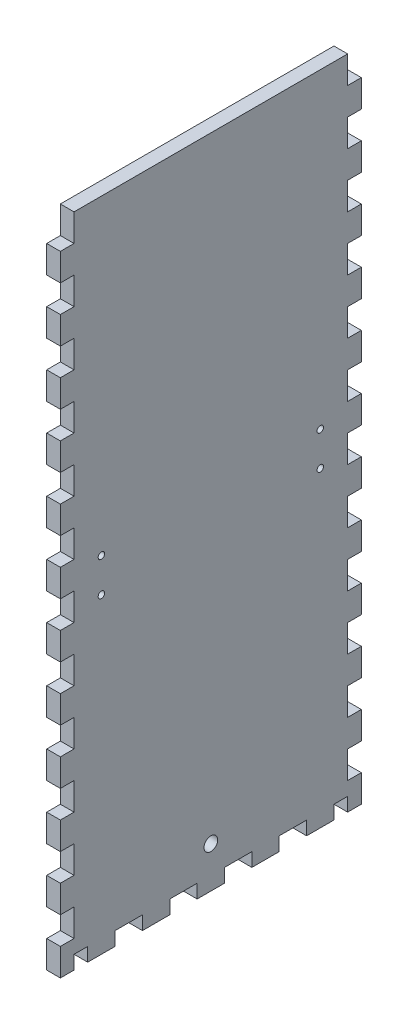
SolidWorks part; units mm, degrees
material "Acrylic (Medium-high impact)"
ref_plane "Front Plane" through (0, 0, 0) normal (0, 0, 1) x (1, 0, 0)
ref_plane "Top Plane" through (0, 0, 0) normal (0, 1, 0) x (1, 0, 0)
ref_plane "Right Plane" through (0, 0, 0) normal (1, 0, 0) x (0, 0, -1)
sketch "Sketch1" plane through (0, 0, 0) normal (0, 1, 0) x (1, 0, 0)
  line L1 (-136.525, 69.85) -> (136.525, 69.85)
  line L2 (-136.525, 69.85) -> (-136.525, -69.85)
  line L3 (-136.525, -69.85) -> (136.525, -69.85)
  line L4 (136.525, 69.85) -> (136.525, -69.85)
  point P4 (-136.525, 0)
  point P6 (0, 69.85)
  dimension "D1" = 139.7
  dimension "D2" = 273.05
extrude "Boss-Extrude1" add sketch "Sketch1" along normal blind 6.35
sketch "Sketch2" plane through (0, 6.35, 0) normal (0, 1, 0) x (1, 0, 0)
  line L0 (136.525, -69.85) -> (136.525, 69.85) construction
  line L1 (-136.525, 69.85) -> (136.525, 69.85)
  line L2 (-136.525, 69.85) -> (-136.525, -69.85)
  line L3 (-136.525, -69.85) -> (136.525, -69.85)
  line L4 (136.525, 69.85) -> (136.525, -69.85)
  line L5 (-136.525, -69.85) -> (136.525, -69.85) construction
  line L7 (-130.175, 63.5) -> (130.175, 63.5)
  line L8 (-130.175, 63.5) -> (-130.175, -63.5)
  line L9 (-130.175, -63.5) -> (130.175, -63.5)
  line L10 (130.175, 63.5) -> (130.175, -63.5)
  point P7 (-130.175, 0)
  point P14 (-136.525, 0)
  point P15 (0, -63.5)
  point P16 (0, -69.85)
  point P17 (130.175, 0)
  point P18 (136.525, 0)
  dimension "D1" = 6.35
  dimension "D2" = 6.35
extrude "Boss-Extrude2" add sketch "Sketch2" along normal blind 298.45
sketch "Sketch3" plane through (0, 0, 69.85) normal (0, 0, 1) x (1, 0, 0)
  line L0 (-25.273, 304.8) -> (-25.273, 0) construction
  line L2 (-130.175, 6.35) -> (130.175, 6.35) construction
  line L4 (-28.575, 283.21) -> (-28.575, 6.35)
  line L5 (-28.575, 6.35) -> (-21.971, 6.35)
  line L6 (-21.971, 292.354) -> (-21.971, 6.35)
  line L7 (-21.971, 292.354) -> (-41.529, 292.354)
  line L9 (-31.115, 285.75) -> (-41.529, 285.75)
  line L10 (-41.529, 292.354) -> (-41.529, 285.75)
  line L11 (-21.971, 101.6) -> (-9.271, 101.6) construction
  line L12 (-136.525, 0) -> (136.525, 0) construction
  line L13 (-12.446, 88.9) -> (-12.446, 101.6) construction
  line L14 (-15.621, 88.9) -> (-9.271, 88.9)
  line L15 (-15.621, 88.9) -> (-15.621, 71.9667)
  line L16 (-15.621, 71.9667) -> (-9.271, 71.9667)
  line L17 (-9.271, 88.9) -> (-9.271, 71.9667)
  line L18 (-15.621, 42.3333) -> (-9.271, 42.3333)
  line L19 (-15.621, 42.3333) -> (-15.621, 59.2667)
  line L20 (-15.621, 59.2667) -> (-9.271, 59.2667)
  line L21 (-9.271, 42.3333) -> (-9.271, 59.2667)
  line L26 (-15.621, 29.6333) -> (-9.271, 29.6333)
  line L27 (-15.621, 29.6333) -> (-15.621, 12.7)
  line L28 (-15.621, 12.7) -> (-9.271, 12.7)
  line L29 (-9.271, 29.6333) -> (-9.271, 12.7)
  line L30 (-12.446, 59.2667) -> (-12.446, 71.9667) construction
  line L31 (-12.446, 29.6333) -> (-12.446, 42.3333) construction
  line L32 (-12.446, 12.7) -> (-12.446, 0) construction
  line L33 (-136.525, 304.8) -> (136.525, 304.8) construction
  line L34 (-130.175, 304.8) -> (-130.175, 6.35) construction
  arc A0 (-28.575, 283.21) -> (-31.115, 285.75) centre (-31.115, 283.21) ccw
  point P5 (-25.273, 6.35)
  dimension "D5" = 2.54
  dimension "D1" = 6.604
  dimension "D2" = 12.954
  dimension "D3" = 6.604
  dimension "D4" = 286.004
  dimension "D6" = 101.6
  dimension "D7" = 12.7
  dimension "D8" = 12.7
  dimension "D9" = 6.35
  dimension "D10" = 101.6
extrude "Door Slot" cut sketch "Sketch3" against normal blind 12.7
sketch "Sketch4" plane through (0, 0, -63.5) normal (0, 0, 1) x (1, 0, 0)
  line L0 (-136.525, 304.8) -> (136.525, 304.8) construction
  line L1 (-47.879, 304.8) -> (-41.529, 304.8)
  line L2 (-47.879, 304.8) -> (-47.879, 6.35)
  line L3 (-47.879, 6.35) -> (-41.529, 6.35)
  line L4 (-41.529, 304.8) -> (-41.529, 6.35)
  line L5 (-18.796, 263.525) -> (-18.796, 247.65) construction
  line L6 (-41.529, 292.354) -> (-41.529, 285.75) construction
  line L7 (-21.971, 304.8) -> (-15.621, 304.8)
  line L8 (-21.971, 304.8) -> (-21.971, 6.35)
  line L9 (-21.971, 6.35) -> (-15.621, 6.35)
  line L10 (-15.621, 304.8) -> (-15.621, 6.35)
  line L11 (130.175, 6.35) -> (-130.175, 6.35) construction
  line L12 (-21.971, 6.35) -> (-21.971, 292.354) construction
  line L13 (-41.529, 304.8) -> (-47.879, 304.8)
  line L14 (-41.529, 304.8) -> (-41.529, 292.1)
  line L15 (-41.529, 292.1) -> (-47.879, 292.1)
  line L16 (-47.879, 304.8) -> (-47.879, 292.1)
  line L17 (-41.529, 276.225) -> (-47.879, 276.225)
  line L18 (-41.529, 276.225) -> (-41.529, 263.525)
  line L19 (-41.529, 263.525) -> (-47.879, 263.525)
  line L20 (-47.879, 276.225) -> (-47.879, 263.525)
  line L21 (-47.879, 6.35) -> (-41.529, 6.35)
  line L22 (-47.879, 6.35) -> (-47.879, 19.05)
  line L23 (-47.879, 19.05) -> (-41.529, 19.05)
  line L24 (-41.529, 6.35) -> (-41.529, 19.05)
  line L25 (-47.879, 34.925) -> (-41.529, 34.925)
  line L26 (-47.879, 34.925) -> (-47.879, 47.625)
  line L27 (-47.879, 47.625) -> (-41.529, 47.625)
  line L28 (-41.529, 34.925) -> (-41.529, 47.625)
  line L29 (-47.879, 92.075) -> (-41.529, 92.075)
  line L30 (-47.879, 92.075) -> (-47.879, 104.775)
  line L31 (-47.879, 104.775) -> (-41.529, 104.775)
  line L32 (-41.529, 92.075) -> (-41.529, 104.775)
  line L33 (-47.879, 149.225) -> (-41.529, 149.225)
  line L34 (-47.879, 149.225) -> (-47.879, 161.925)
  line L35 (-47.879, 161.925) -> (-41.529, 161.925)
  line L36 (-41.529, 149.225) -> (-41.529, 161.925)
  line L37 (-47.879, 177.8) -> (-41.529, 177.8)
  line L38 (-47.879, 177.8) -> (-47.879, 190.5)
  line L39 (-47.879, 190.5) -> (-41.529, 190.5)
  line L40 (-41.529, 177.8) -> (-41.529, 190.5)
  line L41 (-47.879, 206.375) -> (-41.529, 206.375)
  line L42 (-47.879, 206.375) -> (-47.879, 219.075)
  line L43 (-47.879, 219.075) -> (-41.529, 219.075)
  line L44 (-41.529, 206.375) -> (-41.529, 219.075)
  line L45 (-47.879, 234.95) -> (-41.529, 234.95)
  line L46 (-47.879, 234.95) -> (-47.879, 247.65)
  line L47 (-47.879, 247.65) -> (-41.529, 247.65)
  line L48 (-41.529, 234.95) -> (-41.529, 247.65)
  line L49 (-41.529, 133.35) -> (-47.879, 133.35)
  line L50 (-41.529, 133.35) -> (-41.529, 120.65)
  line L51 (-41.529, 120.65) -> (-47.879, 120.65)
  line L52 (-47.879, 133.35) -> (-47.879, 120.65)
  line L53 (-41.529, 76.2) -> (-47.879, 76.2)
  line L54 (-41.529, 76.2) -> (-41.529, 63.5)
  line L55 (-41.529, 63.5) -> (-47.879, 63.5)
  line L56 (-47.879, 76.2) -> (-47.879, 63.5)
  line L57 (-44.704, 304.8) -> (-44.704, 292.1) construction
  line L58 (-44.704, 292.1) -> (-44.704, 276.225) construction
  line L59 (-44.704, 276.225) -> (-44.704, 263.525) construction
  line L60 (-44.704, 247.65) -> (-44.704, 234.95) construction
  line L61 (-44.704, 234.95) -> (-44.704, 219.075) construction
  line L62 (-44.704, 219.075) -> (-44.704, 206.375) construction
  line L63 (-44.704, 206.375) -> (-44.704, 190.5) construction
  line L64 (-44.704, 190.5) -> (-44.704, 177.8) construction
  line L65 (-44.704, 177.8) -> (-44.704, 161.925) construction
  line L66 (-44.704, 161.925) -> (-44.704, 149.225) construction
  line L67 (-44.704, 133.35) -> (-44.704, 120.65) construction
  line L68 (-44.704, 120.65) -> (-44.704, 104.775) construction
  line L69 (-44.704, 104.775) -> (-44.704, 92.075) construction
  line L70 (-44.704, 92.075) -> (-44.704, 76.2) construction
  line L71 (-44.704, 76.2) -> (-44.704, 63.5) construction
  line L72 (-44.704, 63.5) -> (-44.704, 47.625) construction
  line L73 (-44.704, 47.625) -> (-44.704, 34.925) construction
  line L74 (-44.704, 34.925) -> (-44.704, 19.05) construction
  line L75 (-44.704, 19.05) -> (-44.704, 6.35) construction
  line L76 (-44.704, 149.225) -> (-44.704, 133.35) construction
  line L77 (-44.704, 263.525) -> (-44.704, 247.65) construction
  line L78 (-31.75, 304.8) -> (-31.75, 0) construction
  line L79 (136.525, 304.8) -> (-136.525, 304.8) construction
  line L80 (136.525, 0) -> (-136.525, 0) construction
  line L81 (-31.75, 8.3493) -> (-21.971, 8.3493) construction
  line L82 (-31.75, 8.3493) -> (-41.529, 8.3493) construction
  line L83 (-18.796, 149.225) -> (-18.796, 133.35) construction
  line L84 (-18.796, 19.05) -> (-18.796, 6.35) construction
  line L85 (-18.796, 34.925) -> (-18.796, 19.05) construction
  line L86 (-18.796, 47.625) -> (-18.796, 34.925) construction
  line L87 (-18.796, 63.5) -> (-18.796, 47.625) construction
  line L88 (-18.796, 76.2) -> (-18.796, 63.5) construction
  line L89 (-18.796, 92.075) -> (-18.796, 76.2) construction
  line L90 (-18.796, 104.775) -> (-18.796, 92.075) construction
  line L91 (-18.796, 120.65) -> (-18.796, 104.775) construction
  line L92 (-18.796, 133.35) -> (-18.796, 120.65) construction
  line L93 (-18.796, 161.925) -> (-18.796, 149.225) construction
  line L94 (-18.796, 177.8) -> (-18.796, 161.925) construction
  line L95 (-18.796, 190.5) -> (-18.796, 177.8) construction
  line L96 (-18.796, 206.375) -> (-18.796, 190.5) construction
  line L97 (-18.796, 219.075) -> (-18.796, 206.375) construction
  line L98 (-18.796, 234.95) -> (-18.796, 219.075) construction
  line L99 (-18.796, 247.65) -> (-18.796, 234.95) construction
  line L100 (-18.796, 276.225) -> (-18.796, 263.525) construction
  line L101 (-18.796, 292.1) -> (-18.796, 276.225) construction
  line L102 (-18.796, 304.8) -> (-18.796, 292.1) construction
  line L103 (-15.621, 76.2) -> (-15.621, 63.5)
  line L104 (-21.971, 63.5) -> (-15.621, 63.5)
  line L105 (-21.971, 76.2) -> (-21.971, 63.5)
  line L106 (-21.971, 76.2) -> (-15.621, 76.2)
  line L107 (-15.621, 133.35) -> (-15.621, 120.65)
  line L108 (-21.971, 120.65) -> (-15.621, 120.65)
  line L109 (-21.971, 133.35) -> (-21.971, 120.65)
  line L110 (-21.971, 133.35) -> (-15.621, 133.35)
  line L111 (-21.971, 234.95) -> (-21.971, 247.65)
  line L112 (-15.621, 247.65) -> (-21.971, 247.65)
  line L113 (-15.621, 234.95) -> (-15.621, 247.65)
  line L114 (-15.621, 234.95) -> (-21.971, 234.95)
  line L115 (-21.971, 206.375) -> (-21.971, 219.075)
  line L116 (-15.621, 219.075) -> (-21.971, 219.075)
  line L117 (-15.621, 206.375) -> (-15.621, 219.075)
  line L118 (-15.621, 206.375) -> (-21.971, 206.375)
  line L119 (-21.971, 177.8) -> (-21.971, 190.5)
  line L120 (-15.621, 190.5) -> (-21.971, 190.5)
  line L121 (-15.621, 177.8) -> (-15.621, 190.5)
  line L122 (-15.621, 177.8) -> (-21.971, 177.8)
  line L123 (-21.971, 149.225) -> (-21.971, 161.925)
  line L124 (-15.621, 161.925) -> (-21.971, 161.925)
  line L125 (-15.621, 149.225) -> (-15.621, 161.925)
  line L126 (-15.621, 149.225) -> (-21.971, 149.225)
  line L127 (-21.971, 92.075) -> (-21.971, 104.775)
  line L128 (-15.621, 104.775) -> (-21.971, 104.775)
  line L129 (-15.621, 92.075) -> (-15.621, 104.775)
  line L130 (-15.621, 92.075) -> (-21.971, 92.075)
  line L131 (-21.971, 34.925) -> (-21.971, 47.625)
  line L132 (-15.621, 47.625) -> (-21.971, 47.625)
  line L133 (-15.621, 34.925) -> (-15.621, 47.625)
  line L134 (-15.621, 34.925) -> (-21.971, 34.925)
  line L135 (-21.971, 6.35) -> (-21.971, 19.05)
  line L136 (-15.621, 19.05) -> (-21.971, 19.05)
  line L137 (-15.621, 6.35) -> (-15.621, 19.05)
  line L138 (-15.621, 6.35) -> (-21.971, 6.35)
  line L139 (-15.621, 276.225) -> (-15.621, 263.525)
  line L140 (-21.971, 263.525) -> (-15.621, 263.525)
  line L141 (-21.971, 276.225) -> (-21.971, 263.525)
  line L142 (-21.971, 276.225) -> (-15.621, 276.225)
  line L143 (-15.621, 304.8) -> (-15.621, 292.1)
  line L144 (-21.971, 292.1) -> (-15.621, 292.1)
  line L145 (-21.971, 304.8) -> (-21.971, 292.1)
  line L146 (-21.971, 304.8) -> (-15.621, 304.8)
  line L147 (-21.971, 304.8) -> (-21.971, 6.35)
  line L148 (-15.621, 6.35) -> (-21.971, 6.35)
  line L149 (-15.621, 304.8) -> (-15.621, 6.35)
  line L150 (-15.621, 304.8) -> (-21.971, 304.8)
  point P14 (-41.529, 289.052)
  dimension "D1" = 6.35
  dimension "D2" = 12.7
extrude "Door Guide Holes" cut sketch "Sketch4" against normal up to next contours L17 L4 L15 L2 | L2 L47 L4 L19 | L45 L2 L43 L4 | L41 L2 L39 L4 | L37 L2 L35 L4 | L49 L4 L33 L2 | L4 L51 L2 L31 | L53 L4 L29 L2 | L4 L55 L2 L27 | L25 L2 L23 L4 region at (-44.704, 284.1625, -63.5) region at (-44.704, 255.5875, -63.5) region at (-44.704, 227.0125, -63.5) region at (-44.704, 198.4375, -63.5) region at (-44.704, 169.8625, -63.5) region at (-44.704, 141.2875, -63.5) region at (-44.704, 112.7125, -63.5) region at (-44.704, 84.1375, -63.5) region at (-44.704, 55.5625, -63.5) region at (-44.704, 26.9875, -63.5)
ref_plane "Plane1" through (-31.75, 0, 0) normal (-1, 0, 0) x (0, 0, 1)
mirror "Mirror1" about plane through (-31.75, 0, 0) normal (-1, 0, 0) of "Door Guide Holes"
sketch "Lever Holes" plane through (0, 0, 69.85) normal (0, 0, 1) x (1, 0, 0)
  line L0 (49.276, 31.75) -> (58.928, 31.75)
  line L1 (49.276, 31.75) -> (49.276, 25.4)
  line L2 (49.276, 25.4) -> (58.928, 25.4)
  line L3 (58.928, 31.75) -> (58.928, 25.4)
  line L4 (36.1315, 19.05) -> (42.4815, 19.05)
  line L5 (36.1315, 19.05) -> (36.1315, 12.7)
  line L6 (36.1315, 12.7) -> (42.4815, 12.7)
  line L7 (42.4815, 19.05) -> (42.4815, 12.7)
  line L8 (65.7225, 19.05) -> (72.0725, 19.05)
  line L9 (65.7225, 19.05) -> (65.7225, 12.7)
  line L10 (65.7225, 12.7) -> (72.0725, 12.7)
  line L11 (72.0725, 19.05) -> (72.0725, 12.7)
  line L12 (42.4815, 15.875) -> (65.7225, 15.875) construction
  line L13 (-136.525, 0) -> (136.525, 0) construction
  line L14 (-21.971, 6.35) -> (130.175, 6.35) construction
  line L15 (130.175, 6.35) -> (-130.175, 6.35) construction
  point P12 (54.102, 15.875)
  point P13 (54.102, 25.4)
  point P24 (54.102, 6.35)
  dimension "D1" = 9.652
  dimension "D2" = 6.35
  dimension "D3" = 6.35
  dimension "D4" = 6.35
  dimension "D5" = 23.241
  dimension "D6" = 25.4
  dimension "D7" = 12.7
extrude "Cut-Extrude1" cut sketch "Lever Holes" against normal through all
sketch "Sketch7" plane through (136.525, 0, 0) normal (1, 0, 0) x (0, 0, -1)
  line L0 (-37.211, 92.583) -> (37.211, 92.583)
  line L1 (-37.211, 92.583) -> (-37.211, 18.161)
  line L2 (-37.211, 18.161) -> (37.211, 18.161)
  line L3 (37.211, 92.583) -> (37.211, 18.161)
  line L4 (-69.85, 0) -> (69.85, 0) construction
  circle A0 centre (0, 55.372) radius 26.9875
  circle A1 centre (-37.211, 92.583) radius 3.175
  circle A2 centre (37.211, 92.583) radius 3.175
  circle A3 centre (-37.211, 18.161) radius 3.175
  circle A4 centre (37.211, 18.161) radius 3.175
  point P9 (0, 18.161)
  point P10 (-37.211, 55.372)
  dimension "D3" = 53.975
  dimension "D4" = 6.35
  dimension "D1" = 74.422
  dimension "D2" = 55.372
extrude "Cut-Extrude2" cut sketch "Sketch7" against normal up to next contours A0 | L0 A1 L1 | L1 A1 L0 | L3 A2 L0 | L0 A2 L3 | L2 A3 L1 | L1 A3 L2 | L2 A4 L3 | L3 A4 L2 region at (136.525, 93.0322, 37.6602) region at (136.525, 91.2355, 35.8635) region at (136.525, 93.0322, -37.6602) region at (136.525, 91.2355, -35.8635) region at (136.525, 19.5085, 35.8635) region at (136.525, 17.7118, 37.6602) region at (136.525, 17.7118, -37.6602) region at (136.525, 19.5085, -35.8635) region at (136.525, 55.372, 0)
sketch "Sketch8" plane through (-136.525, 0, 0) normal (-1, 0, 0) x (0, 0, 1)
  line L0 (-69.85, 0) -> (69.85, 0) construction
  line L1 (-50.8, 160.275) -> (-50.8, 144.525) construction
  line L2 (-69.85, 304.8) -> (-69.85, 0) construction
  line L3 (0, -150.1775) -> (0, 150.1775) construction
  circle A0 centre (0, 19.05) radius 3.175
  circle A1 centre (-50.8, 160.275) radius 1.5
  circle A2 centre (-50.8, 144.525) radius 1.5
  circle A3 centre (50.8, 144.525) radius 1.5
  circle A4 centre (50.8, 160.275) radius 1.5
  point P6 (0, 0)
  point P12 (-50.8, 152.4)
  point P13 (-69.85, 152.4)
  dimension "D1" = 6.35
  dimension "D4" = 3
  dimension "D2" = 19.05
  dimension "D3" = 15.75
  dimension "D5" = 19.05
extrude "Cut-Extrude3" cut sketch "Sketch8" against normal up to next
sketch "Bottom" plane through (0, 0, 0) normal (0, -1, 0) x (1, 0, 0)
  line L0 (-130.175, 63.5) -> (130.175, 63.5) construction
  line L1 (-136.525, 69.85) -> (-122.1539, 69.85)
  line L2 (-136.525, 69.85) -> (-136.525, 63.5)
  line L3 (-136.525, 63.5) -> (-122.1539, 63.5)
  line L4 (-122.1539, 69.85) -> (-122.1539, 63.5)
  line L5 (-122.1539, 69.85) -> (-107.7829, 69.85)
  line L6 (-122.1539, 69.85) -> (-122.1539, 63.5)
  line L7 (-122.1539, 63.5) -> (-107.7829, 63.5)
  line L8 (-107.7829, 69.85) -> (-107.7829, 63.5)
  line L9 (-107.7829, 69.85) -> (-93.4118, 69.85)
  line L10 (-107.7829, 69.85) -> (-107.7829, 63.5)
  line L11 (-107.7829, 63.5) -> (-93.4118, 63.5)
  line L12 (-93.4118, 69.85) -> (-93.4118, 63.5)
  line L13 (-93.4118, 69.85) -> (-79.0408, 69.85)
  line L14 (-93.4118, 69.85) -> (-93.4118, 63.5)
  line L15 (-93.4118, 63.5) -> (-79.0408, 63.5)
  line L16 (-79.0408, 69.85) -> (-79.0408, 63.5)
  line L17 (-136.525, 69.85) -> (136.525, 69.85) construction
  line L18 (-41.529, 63.5) -> (-21.971, 63.5) construction
  line L19 (-79.0408, 69.85) -> (-64.6697, 69.85)
  line L20 (-79.0408, 69.85) -> (-79.0408, 63.5)
  line L21 (-79.0408, 63.5) -> (-64.6697, 63.5)
  line L22 (-64.6697, 69.85) -> (-64.6697, 63.5)
  line L23 (-64.6697, 69.85) -> (-50.2987, 69.85)
  line L24 (-64.6697, 69.85) -> (-64.6697, 63.5)
  line L25 (-64.6697, 63.5) -> (-50.2987, 63.5)
  line L26 (-50.2987, 69.85) -> (-50.2987, 63.5)
  line L27 (-50.2987, 69.85) -> (-35.9276, 69.85)
  line L28 (-50.2987, 69.85) -> (-50.2987, 63.5)
  line L29 (-50.2987, 63.5) -> (-35.9276, 63.5)
  line L30 (-35.9276, 69.85) -> (-35.9276, 63.5)
  line L31 (-35.9276, 69.85) -> (-21.5566, 69.85)
  line L32 (-35.9276, 69.85) -> (-35.9276, 63.5)
  line L33 (-35.9276, 63.5) -> (-21.5566, 63.5)
  line L34 (-21.5566, 69.85) -> (-21.5566, 63.5)
  line L36 (-21.5566, 69.85) -> (-7.1855, 69.85)
  line L37 (-21.5566, 69.85) -> (-21.5566, 63.5)
  line L38 (-21.5566, 63.5) -> (-7.1855, 63.5)
  line L39 (-7.1855, 69.85) -> (-7.1855, 63.5)
  line L40 (-7.1855, 69.85) -> (7.1855, 69.85)
  line L41 (-7.1855, 69.85) -> (-7.1855, 63.5)
  line L42 (-7.1855, 63.5) -> (7.1855, 63.5)
  line L43 (7.1855, 69.85) -> (7.1855, 63.5)
  line L44 (7.1855, 69.85) -> (21.5566, 69.85)
  line L45 (7.1855, 69.85) -> (7.1855, 63.5)
  line L46 (7.1855, 63.5) -> (21.5566, 63.5)
  line L47 (21.5566, 69.85) -> (21.5566, 63.5)
  line L48 (21.5566, 69.85) -> (35.9276, 69.85)
  line L49 (21.5566, 69.85) -> (21.5566, 63.5)
  line L50 (21.5566, 63.5) -> (35.9276, 63.5)
  line L51 (35.9276, 69.85) -> (35.9276, 63.5)
  line L52 (35.9276, 69.85) -> (50.2987, 69.85)
  line L53 (35.9276, 69.85) -> (35.9276, 63.5)
  line L54 (35.9276, 63.5) -> (50.2987, 63.5)
  line L55 (50.2987, 69.85) -> (50.2987, 63.5)
  line L56 (50.2987, 69.85) -> (64.6697, 69.85)
  line L57 (50.2987, 69.85) -> (50.2987, 63.5)
  line L58 (50.2987, 63.5) -> (64.6697, 63.5)
  line L59 (64.6697, 69.85) -> (64.6697, 63.5)
  line L60 (64.6697, 69.85) -> (79.0408, 69.85)
  line L61 (64.6697, 69.85) -> (64.6697, 63.5)
  line L62 (64.6697, 63.5) -> (79.0408, 63.5)
  line L63 (79.0408, 69.85) -> (79.0408, 63.5)
  line L64 (79.0408, 69.85) -> (93.4118, 69.85)
  line L65 (79.0408, 69.85) -> (79.0408, 63.5)
  line L66 (79.0408, 63.5) -> (93.4118, 63.5)
  line L67 (93.4118, 69.85) -> (93.4118, 63.5)
  line L68 (93.4118, 69.85) -> (107.7829, 69.85)
  line L69 (93.4118, 69.85) -> (93.4118, 63.5)
  line L70 (93.4118, 63.5) -> (107.7829, 63.5)
  line L71 (107.7829, 69.85) -> (107.7829, 63.5)
  line L72 (107.7829, 69.85) -> (122.1539, 69.85)
  line L73 (107.7829, 69.85) -> (107.7829, 63.5)
  line L74 (107.7829, 63.5) -> (122.1539, 63.5)
  line L75 (122.1539, 69.85) -> (122.1539, 63.5)
  line L76 (-130.175, -63.5) -> (-130.175, 63.5) construction
  line L77 (-136.525, 69.85) -> (-130.175, 69.85)
  line L78 (-136.525, 69.85) -> (-136.525, 57.15)
  line L79 (-136.525, 57.15) -> (-130.175, 57.15)
  line L80 (-130.175, 69.85) -> (-130.175, 57.15)
  line L82 (-136.525, 57.15) -> (-130.175, 57.15)
  line L83 (-136.525, 57.15) -> (-136.525, 44.45)
  line L84 (-136.525, 44.45) -> (-130.175, 44.45)
  line L85 (-130.175, 57.15) -> (-130.175, 44.45)
  line L86 (-136.525, 44.45) -> (-130.175, 44.45)
  line L87 (-136.525, 44.45) -> (-136.525, 31.75)
  line L88 (-136.525, 31.75) -> (-130.175, 31.75)
  line L89 (-130.175, 44.45) -> (-130.175, 31.75)
  line L90 (-136.525, 31.75) -> (-130.175, 31.75)
  line L91 (-136.525, 31.75) -> (-136.525, 19.05)
  line L92 (-136.525, 19.05) -> (-130.175, 19.05)
  line L93 (-130.175, 31.75) -> (-130.175, 19.05)
  line L94 (-136.525, 19.05) -> (-130.175, 19.05)
  line L95 (-136.525, 19.05) -> (-136.525, 6.35)
  line L96 (-136.525, 6.35) -> (-130.175, 6.35)
  line L97 (-130.175, 19.05) -> (-130.175, 6.35)
  line L98 (-136.525, 6.35) -> (-130.175, 6.35)
  line L99 (-136.525, 6.35) -> (-136.525, -6.35)
  line L100 (-136.525, -6.35) -> (-130.175, -6.35)
  line L101 (-130.175, 6.35) -> (-130.175, -6.35)
  line L102 (-136.525, -6.35) -> (-130.175, -6.35)
  line L103 (-136.525, -6.35) -> (-136.525, -19.05)
  line L104 (-136.525, -19.05) -> (-130.175, -19.05)
  line L105 (-130.175, -6.35) -> (-130.175, -19.05)
  line L106 (-136.525, -19.05) -> (-130.175, -19.05)
  line L107 (-136.525, -19.05) -> (-136.525, -31.75)
  line L108 (-136.525, -31.75) -> (-130.175, -31.75)
  line L109 (-130.175, -19.05) -> (-130.175, -31.75)
  line L110 (-136.525, -31.75) -> (-130.175, -31.75)
  line L111 (-136.525, -31.75) -> (-136.525, -44.45)
  line L112 (-136.525, -44.45) -> (-130.175, -44.45)
  line L113 (-130.175, -31.75) -> (-130.175, -44.45)
  line L114 (-136.525, -44.45) -> (-130.175, -44.45)
  line L115 (-136.525, -44.45) -> (-136.525, -57.15)
  line L116 (-136.525, -57.15) -> (-130.175, -57.15)
  line L117 (-130.175, -44.45) -> (-130.175, -57.15)
  line L118 (136.525, 69.85) -> (136.525, -69.85) construction
  line L119 (122.1539, 69.85) -> (136.525, 69.85)
  line L120 (122.1539, 69.85) -> (122.1539, 63.5)
  line L121 (122.1539, 63.5) -> (136.525, 63.5)
  line L122 (136.525, 69.85) -> (136.525, 63.5)
  line L123 (136.525, -69.85) -> (-136.525, -69.85) construction
  line L124 (-136.525, -57.15) -> (-130.175, -57.15)
  line L125 (-136.525, -57.15) -> (-136.525, -69.85)
  line L126 (-136.525, -69.85) -> (-130.175, -69.85)
  line L127 (-130.175, -57.15) -> (-130.175, -69.85)
  line L128 (150.1775, 0) -> (-150.1775, 0) construction
  line L129 (136.525, -69.85) -> (136.525, -63.5)
  line L130 (122.1539, -63.5) -> (136.525, -63.5)
  line L131 (122.1539, -69.85) -> (136.525, -69.85)
  line L132 (122.1539, -69.85) -> (122.1539, -63.5)
  line L133 (107.7829, -63.5) -> (122.1539, -63.5)
  line L134 (107.7829, -69.85) -> (122.1539, -69.85)
  line L135 (107.7829, -69.85) -> (107.7829, -63.5)
  line L136 (93.4118, -63.5) -> (107.7829, -63.5)
  line L137 (93.4118, -69.85) -> (107.7829, -69.85)
  line L138 (93.4118, -69.85) -> (93.4118, -63.5)
  line L139 (79.0408, -63.5) -> (93.4118, -63.5)
  line L140 (79.0408, -69.85) -> (93.4118, -69.85)
  line L141 (79.0408, -69.85) -> (79.0408, -63.5)
  line L142 (64.6697, -63.5) -> (79.0408, -63.5)
  line L143 (64.6697, -69.85) -> (79.0408, -69.85)
  line L144 (50.2987, -63.5) -> (64.6697, -63.5)
  line L145 (64.6697, -69.85) -> (64.6697, -63.5)
  line L146 (50.2987, -69.85) -> (64.6697, -69.85)
  line L147 (50.2987, -69.85) -> (50.2987, -63.5)
  line L148 (35.9276, -63.5) -> (50.2987, -63.5)
  line L149 (35.9276, -69.85) -> (50.2987, -69.85)
  line L150 (35.9276, -69.85) -> (35.9276, -63.5)
  line L151 (21.5566, -63.5) -> (35.9276, -63.5)
  line L152 (21.5566, -69.85) -> (35.9276, -69.85)
  line L153 (21.5566, -69.85) -> (21.5566, -63.5)
  line L154 (7.1855, -69.85) -> (21.5566, -69.85)
  line L155 (7.1855, -63.5) -> (21.5566, -63.5)
  line L156 (7.1855, -69.85) -> (7.1855, -63.5)
  line L157 (-7.1855, -63.5) -> (7.1855, -63.5)
  line L158 (-7.1855, -69.85) -> (7.1855, -69.85)
  line L159 (-21.5566, -63.5) -> (-7.1855, -63.5)
  line L160 (-7.1855, -69.85) -> (-7.1855, -63.5)
  line L161 (-21.5566, -69.85) -> (-7.1855, -69.85)
  line L162 (-21.5566, -69.85) -> (-21.5566, -63.5)
  line L163 (-35.9276, -63.5) -> (-21.5566, -63.5)
  line L164 (-35.9276, -69.85) -> (-21.5566, -69.85)
  line L165 (-35.9276, -69.85) -> (-35.9276, -63.5)
  line L166 (-50.2987, -63.5) -> (-35.9276, -63.5)
  line L167 (-50.2987, -69.85) -> (-35.9276, -69.85)
  line L168 (-50.2987, -69.85) -> (-50.2987, -63.5)
  line L169 (-64.6697, -69.85) -> (-50.2987, -69.85)
  line L170 (-64.6697, -63.5) -> (-50.2987, -63.5)
  line L171 (-79.0408, -63.5) -> (-64.6697, -63.5)
  line L172 (-64.6697, -69.85) -> (-64.6697, -63.5)
  line L173 (-79.0408, -69.85) -> (-64.6697, -69.85)
  line L174 (-93.4118, -69.85) -> (-79.0408, -69.85)
  line L175 (-93.4118, -63.5) -> (-79.0408, -63.5)
  line L176 (-79.0408, -69.85) -> (-79.0408, -63.5)
  line L177 (-107.7829, -69.85) -> (-107.7829, -63.5)
  line L178 (-107.7829, -69.85) -> (-93.4118, -69.85)
  line L179 (-93.4118, -69.85) -> (-93.4118, -63.5)
  line L180 (-107.7829, -63.5) -> (-93.4118, -63.5)
  line L181 (-122.1539, -63.5) -> (-107.7829, -63.5)
  line L182 (-122.1539, -69.85) -> (-107.7829, -69.85)
  line L183 (-122.1539, -69.85) -> (-122.1539, -63.5)
  line L184 (-136.525, -69.85) -> (-122.1539, -69.85)
  line L185 (-136.525, -69.85) -> (-136.525, -63.5)
  line L186 (-136.525, -63.5) -> (-122.1539, -63.5)
  line L187 (0, -76.835) -> (0, 76.835) construction
  line L188 (136.525, -69.85) -> (130.175, -69.85)
  line L189 (130.175, -57.15) -> (130.175, -69.85)
  line L190 (136.525, -57.15) -> (136.525, -69.85)
  line L191 (136.525, -57.15) -> (130.175, -57.15)
  line L192 (130.175, -44.45) -> (130.175, -57.15)
  line L193 (136.525, -44.45) -> (136.525, -57.15)
  line L194 (136.525, -44.45) -> (130.175, -44.45)
  line L195 (130.175, -31.75) -> (130.175, -44.45)
  line L196 (136.525, -31.75) -> (136.525, -44.45)
  line L197 (136.525, -31.75) -> (130.175, -31.75)
  line L198 (136.525, -19.05) -> (136.525, -31.75)
  line L199 (130.175, -19.05) -> (130.175, -31.75)
  line L200 (130.175, -6.35) -> (130.175, -19.05)
  line L201 (136.525, -6.35) -> (136.525, -19.05)
  line L202 (136.525, -19.05) -> (130.175, -19.05)
  line L203 (136.525, -6.35) -> (130.175, -6.35)
  line L204 (130.175, 6.35) -> (130.175, -6.35)
  line L205 (136.525, 6.35) -> (136.525, -6.35)
  line L206 (136.525, 6.35) -> (130.175, 6.35)
  line L207 (130.175, 19.05) -> (130.175, 6.35)
  line L208 (136.525, 19.05) -> (136.525, 6.35)
  line L209 (136.525, 19.05) -> (130.175, 19.05)
  line L210 (136.525, 31.75) -> (130.175, 31.75)
  line L211 (136.525, 44.45) -> (130.175, 44.45)
  line L212 (136.525, 57.15) -> (130.175, 57.15)
  line L213 (130.175, 31.75) -> (130.175, 19.05)
  line L214 (136.525, 31.75) -> (136.525, 19.05)
  line L215 (130.175, 44.45) -> (130.175, 31.75)
  line L216 (136.525, 44.45) -> (136.525, 31.75)
  line L217 (130.175, 57.15) -> (130.175, 44.45)
  line L218 (136.525, 57.15) -> (136.525, 44.45)
  line L219 (130.175, 69.85) -> (130.175, 57.15)
  line L220 (136.525, 69.85) -> (136.525, 57.15)
sketch "Front/Back" plane through (0, 0, 69.85) normal (0, 0, 1) x (1, 0, 0)
  line L0 (-130.175, 6.35) -> (-28.575, 6.35) construction
  line L1 (-136.525, 0) -> (-122.1539, 0)
  line L2 (-136.525, 0) -> (-136.525, 6.35)
  line L3 (-136.525, 6.35) -> (-122.1539, 6.35)
  line L4 (-122.1539, 0) -> (-122.1539, 6.35)
  line L5 (-136.525, 0) -> (136.525, 0) construction
  line L6 (-107.7829, 0) -> (-93.4118, 0) construction
  line L7 (-122.1539, 6.35) -> (-107.7829, 6.35)
  line L8 (-122.1539, 6.35) -> (-122.1539, 0)
  line L9 (-122.1539, 0) -> (-107.7829, 0)
  line L10 (-107.7829, 6.35) -> (-107.7829, 0)
  line L11 (-79.0408, 0) -> (-64.6697, 0) construction
  line L12 (-107.7829, 6.35) -> (-93.4118, 6.35)
  line L13 (-107.7829, 6.35) -> (-107.7829, 0)
  line L14 (-107.7829, 0) -> (-93.4118, 0)
  line L15 (-93.4118, 6.35) -> (-93.4118, 0)
  line L16 (-93.4118, 6.35) -> (-79.0408, 6.35)
  line L17 (-93.4118, 6.35) -> (-93.4118, 0)
  line L18 (-93.4118, 0) -> (-79.0408, 0)
  line L19 (-79.0408, 6.35) -> (-79.0408, 0)
  line L20 (-64.6697, 0) -> (-50.2987, 0) construction
  line L21 (-79.0408, 6.35) -> (-64.6697, 6.35)
  line L22 (-79.0408, 6.35) -> (-79.0408, 0)
  line L23 (-79.0408, 0) -> (-64.6697, 0)
  line L24 (-64.6697, 6.35) -> (-64.6697, 0)
  line L25 (-64.6697, 6.35) -> (-50.2987, 6.35)
  line L26 (-64.6697, 6.35) -> (-64.6697, 0)
  line L27 (-64.6697, 0) -> (-50.2987, 0)
  line L28 (-50.2987, 6.35) -> (-50.2987, 0)
  line L29 (-50.2987, 0) -> (-35.9276, 0) construction
  line L30 (-50.2987, 6.35) -> (-35.9276, 6.35)
  line L31 (-50.2987, 6.35) -> (-50.2987, 0)
  line L32 (-50.2987, 0) -> (-35.9276, 0)
  line L33 (-35.9276, 6.35) -> (-35.9276, 0)
  line L34 (-21.5566, 0) -> (-7.1855, 0) construction
  line L35 (-35.9276, 6.35) -> (-21.5566, 6.35)
  line L36 (-35.9276, 6.35) -> (-35.9276, 0)
  line L37 (-35.9276, 0) -> (-21.5566, 0)
  line L38 (-21.5566, 6.35) -> (-21.5566, 0)
  line L39 (7.1855, 0) -> (21.5566, 0) construction
  line L40 (-21.5566, 6.35) -> (-7.1855, 6.35)
  line L41 (-21.5566, 6.35) -> (-21.5566, 0)
  line L42 (-21.5566, 0) -> (-7.1855, 0)
  line L43 (-7.1855, 6.35) -> (-7.1855, 0)
  line L44 (-7.1855, 6.35) -> (7.1855, 6.35)
  line L45 (-7.1855, 6.35) -> (-7.1855, 0)
  line L46 (-7.1855, 0) -> (7.1855, 0)
  line L47 (7.1855, 6.35) -> (7.1855, 0)
  line L48 (7.1855, 0) -> (21.5566, 0) construction
  line L49 (35.9276, 0) -> (50.2987, 0) construction
  line L50 (7.1855, 6.35) -> (21.5566, 6.35)
  line L51 (7.1855, 6.35) -> (7.1855, 0)
  line L52 (7.1855, 0) -> (21.5566, 0)
  line L53 (21.5566, 6.35) -> (21.5566, 0)
  line L54 (21.5566, 6.35) -> (35.9276, 6.35)
  line L55 (21.5566, 6.35) -> (21.5566, 0)
  line L56 (21.5566, 0) -> (35.9276, 0)
  line L57 (35.9276, 6.35) -> (35.9276, 0)
  line L58 (64.6697, 0) -> (79.0408, 0) construction
  line L59 (35.9276, 6.35) -> (50.2987, 6.35)
  line L60 (35.9276, 6.35) -> (35.9276, 0)
  line L61 (35.9276, 0) -> (50.2987, 0)
  line L62 (50.2987, 6.35) -> (50.2987, 0)
  line L63 (50.2987, 6.35) -> (64.6697, 6.35)
  line L64 (50.2987, 6.35) -> (50.2987, 0)
  line L65 (50.2987, 0) -> (64.6697, 0)
  line L66 (64.6697, 6.35) -> (64.6697, 0)
  line L67 (50.2987, 0) -> (64.6697, 0) construction
  line L68 (93.4118, 0) -> (107.7829, 0) construction
  line L69 (64.6697, 6.35) -> (79.0408, 6.35)
  line L70 (64.6697, 6.35) -> (64.6697, 0)
  line L71 (64.6697, 0) -> (79.0408, 0)
  line L72 (79.0408, 6.35) -> (79.0408, 0)
  line L73 (79.0408, 6.35) -> (93.4118, 6.35)
  line L74 (79.0408, 6.35) -> (79.0408, 0)
  line L75 (79.0408, 0) -> (93.4118, 0)
  line L76 (93.4118, 6.35) -> (93.4118, 0)
  line L77 (107.7829, 0) -> (122.1539, 0) construction
  line L78 (93.4118, 6.35) -> (107.7829, 6.35)
  line L79 (93.4118, 6.35) -> (93.4118, 0)
  line L80 (93.4118, 0) -> (107.7829, 0)
  line L81 (107.7829, 6.35) -> (107.7829, 0)
  line L82 (107.7829, 0) -> (122.1539, 0) construction
  line L84 (107.7829, 6.35) -> (122.1539, 6.35)
  line L85 (107.7829, 6.35) -> (107.7829, 0)
  line L86 (107.7829, 0) -> (122.1539, 0)
  line L87 (122.1539, 6.35) -> (122.1539, 0)
  line L88 (122.1539, 6.35) -> (136.525, 6.35)
  line L89 (122.1539, 6.35) -> (122.1539, 0)
  line L90 (122.1539, 0) -> (136.525, 0)
  line L91 (136.525, 6.35) -> (136.525, 0)
  line L92 (-130.175, 304.8) -> (-130.175, 6.35) construction
  line L93 (-136.525, 0) -> (-130.175, 0)
  line L94 (-136.525, 0) -> (-136.525, 12.7)
  line L95 (-136.525, 12.7) -> (-130.175, 12.7)
  line L96 (-130.175, 0) -> (-130.175, 12.7)
  line L97 (-136.525, 304.8) -> (-136.525, 0) construction
  line L98 (-136.525, 12.7) -> (-130.175, 12.7)
  line L99 (-136.525, 12.7) -> (-136.525, 25.4)
  line L100 (-136.525, 25.4) -> (-130.175, 25.4)
  line L101 (-130.175, 12.7) -> (-130.175, 25.4)
  line L102 (-136.525, 25.4) -> (-130.175, 25.4)
  line L103 (-136.525, 25.4) -> (-136.525, 38.1)
  line L104 (-136.525, 38.1) -> (-130.175, 38.1)
  line L105 (-130.175, 25.4) -> (-130.175, 38.1)
  line L106 (-136.525, 38.1) -> (-130.175, 38.1)
  line L107 (-136.525, 38.1) -> (-136.525, 50.8)
  line L108 (-136.525, 50.8) -> (-130.175, 50.8)
  line L109 (-130.175, 38.1) -> (-130.175, 50.8)
  line L110 (-136.525, 50.8) -> (-130.175, 50.8)
  line L111 (-136.525, 50.8) -> (-136.525, 63.5)
  line L112 (-136.525, 63.5) -> (-130.175, 63.5)
  line L113 (-130.175, 50.8) -> (-130.175, 63.5)
  line L114 (-136.525, 63.5) -> (-130.175, 63.5)
  line L115 (-136.525, 63.5) -> (-136.525, 76.2)
  line L116 (-136.525, 76.2) -> (-130.175, 76.2)
  line L117 (-130.175, 63.5) -> (-130.175, 76.2)
  line L118 (-136.525, 76.2) -> (-130.175, 76.2)
  line L119 (-136.525, 76.2) -> (-136.525, 88.9)
  line L120 (-136.525, 88.9) -> (-130.175, 88.9)
  line L121 (-130.175, 76.2) -> (-130.175, 88.9)
  line L122 (-136.525, 88.9) -> (-130.175, 88.9)
  line L123 (-136.525, 88.9) -> (-136.525, 101.6)
  line L124 (-136.525, 101.6) -> (-130.175, 101.6)
  line L125 (-130.175, 88.9) -> (-130.175, 101.6)
  line L126 (-136.525, 101.6) -> (-130.175, 101.6)
  line L127 (-136.525, 101.6) -> (-136.525, 114.3)
  line L128 (-136.525, 114.3) -> (-130.175, 114.3)
  line L129 (-130.175, 101.6) -> (-130.175, 114.3)
  line L130 (-136.525, 114.3) -> (-130.175, 114.3)
  line L131 (-136.525, 114.3) -> (-136.525, 127)
  line L132 (-136.525, 127) -> (-130.175, 127)
  line L133 (-130.175, 114.3) -> (-130.175, 127)
  line L134 (-136.525, 127) -> (-130.175, 127)
  line L135 (-136.525, 127) -> (-136.525, 139.7)
  line L136 (-136.525, 139.7) -> (-130.175, 139.7)
  line L137 (-130.175, 127) -> (-130.175, 139.7)
  line L138 (-136.525, 139.7) -> (-130.175, 139.7)
  line L139 (-136.525, 139.7) -> (-136.525, 152.4)
  line L140 (-136.525, 152.4) -> (-130.175, 152.4)
  line L141 (-130.175, 139.7) -> (-130.175, 152.4)
  line L142 (-136.525, 152.4) -> (-130.175, 152.4)
  line L143 (-136.525, 152.4) -> (-136.525, 165.1)
  line L144 (-136.525, 165.1) -> (-130.175, 165.1)
  line L145 (-130.175, 152.4) -> (-130.175, 165.1)
  line L146 (-136.525, 165.1) -> (-130.175, 165.1)
  line L147 (-136.525, 165.1) -> (-136.525, 177.8)
  line L148 (-136.525, 177.8) -> (-130.175, 177.8)
  line L149 (-130.175, 165.1) -> (-130.175, 177.8)
  line L150 (-136.525, 177.8) -> (-130.175, 177.8)
  line L151 (-136.525, 177.8) -> (-136.525, 190.5)
  line L152 (-136.525, 190.5) -> (-130.175, 190.5)
  line L153 (-130.175, 177.8) -> (-130.175, 190.5)
  line L154 (-136.525, 190.5) -> (-130.175, 190.5)
  line L155 (-136.525, 190.5) -> (-136.525, 203.2)
  line L156 (-136.525, 203.2) -> (-130.175, 203.2)
  line L157 (-130.175, 190.5) -> (-130.175, 203.2)
  line L158 (-136.525, 203.2) -> (-130.175, 203.2)
  line L159 (-136.525, 203.2) -> (-136.525, 215.9)
  line L160 (-136.525, 215.9) -> (-130.175, 215.9)
  line L161 (-130.175, 203.2) -> (-130.175, 215.9)
  line L162 (-136.525, 215.9) -> (-130.175, 215.9)
  line L163 (-136.525, 215.9) -> (-136.525, 228.6)
  line L164 (-136.525, 228.6) -> (-130.175, 228.6)
  line L165 (-130.175, 215.9) -> (-130.175, 228.6)
  line L166 (-136.525, 228.6) -> (-130.175, 228.6)
  line L167 (-136.525, 228.6) -> (-136.525, 241.3)
  line L168 (-136.525, 241.3) -> (-130.175, 241.3)
  line L169 (-130.175, 228.6) -> (-130.175, 241.3)
  line L170 (-136.525, 241.3) -> (-130.175, 241.3)
  line L171 (-136.525, 241.3) -> (-136.525, 254)
  line L172 (-136.525, 254) -> (-130.175, 254)
  line L173 (-130.175, 241.3) -> (-130.175, 254)
  line L174 (-136.525, 254) -> (-130.175, 254)
  line L175 (-136.525, 254) -> (-136.525, 266.7)
  line L176 (-136.525, 266.7) -> (-130.175, 266.7)
  line L177 (-130.175, 254) -> (-130.175, 266.7)
  line L178 (-136.525, 266.7) -> (-130.175, 266.7)
  line L179 (-136.525, 266.7) -> (-136.525, 279.4)
  line L180 (-136.525, 279.4) -> (-130.175, 279.4)
  line L181 (-130.175, 266.7) -> (-130.175, 279.4)
  line L182 (-136.525, 279.4) -> (-130.175, 279.4)
  line L183 (-136.525, 279.4) -> (-136.525, 292.1)
  line L184 (-136.525, 292.1) -> (-130.175, 292.1)
  line L185 (-130.175, 279.4) -> (-130.175, 292.1)
  line L186 (-136.525, 292.1) -> (-130.175, 292.1)
  line L187 (-136.525, 292.1) -> (-136.525, 304.8)
  line L188 (-136.525, 304.8) -> (-130.175, 304.8)
  line L189 (-130.175, 292.1) -> (-130.175, 304.8)
  line L190 (-136.525, 304.8) -> (-130.175, 304.8)
  line L194 (-136.525, 304.8) -> (136.525, 304.8) construction
  line L195 (0, -76.835) -> (0, 76.835) construction
  line L196 (136.525, 304.8) -> (130.175, 304.8)
  line L197 (130.175, 292.1) -> (130.175, 304.8)
  line L198 (136.525, 304.8) -> (130.175, 304.8)
  line L199 (136.525, 292.1) -> (136.525, 304.8)
  line L200 (136.525, 292.1) -> (130.175, 292.1)
  line L201 (130.175, 279.4) -> (130.175, 292.1)
  line L202 (136.525, 292.1) -> (130.175, 292.1)
  line L203 (136.525, 279.4) -> (136.525, 292.1)
  line L204 (136.525, 279.4) -> (130.175, 279.4)
  line L205 (130.175, 266.7) -> (130.175, 279.4)
  line L206 (136.525, 279.4) -> (130.175, 279.4)
  line L207 (136.525, 266.7) -> (136.525, 279.4)
  line L208 (136.525, 266.7) -> (130.175, 266.7)
  line L209 (130.175, 254) -> (130.175, 266.7)
  line L210 (136.525, 266.7) -> (130.175, 266.7)
  line L211 (136.525, 254) -> (136.525, 266.7)
  line L212 (136.525, 254) -> (130.175, 254)
  line L213 (130.175, 241.3) -> (130.175, 254)
  line L214 (136.525, 254) -> (130.175, 254)
  line L215 (136.525, 241.3) -> (136.525, 254)
  line L216 (136.525, 241.3) -> (130.175, 241.3)
  line L217 (130.175, 228.6) -> (130.175, 241.3)
  line L218 (136.525, 241.3) -> (130.175, 241.3)
  line L219 (136.525, 228.6) -> (136.525, 241.3)
  line L220 (136.525, 228.6) -> (130.175, 228.6)
  line L221 (130.175, 215.9) -> (130.175, 228.6)
  line L222 (136.525, 228.6) -> (130.175, 228.6)
  line L223 (136.525, 215.9) -> (136.525, 228.6)
  line L224 (136.525, 215.9) -> (130.175, 215.9)
  line L225 (130.175, 203.2) -> (130.175, 215.9)
  line L226 (136.525, 215.9) -> (130.175, 215.9)
  line L227 (136.525, 203.2) -> (136.525, 215.9)
  line L228 (136.525, 203.2) -> (130.175, 203.2)
  line L229 (130.175, 190.5) -> (130.175, 203.2)
  line L230 (136.525, 203.2) -> (130.175, 203.2)
  line L231 (136.525, 190.5) -> (136.525, 203.2)
  line L232 (136.525, 190.5) -> (130.175, 190.5)
  line L233 (130.175, 177.8) -> (130.175, 190.5)
  line L234 (136.525, 190.5) -> (130.175, 190.5)
  line L235 (136.525, 177.8) -> (136.525, 190.5)
  line L236 (136.525, 177.8) -> (130.175, 177.8)
  line L237 (130.175, 165.1) -> (130.175, 177.8)
  line L238 (136.525, 177.8) -> (130.175, 177.8)
  line L239 (136.525, 165.1) -> (136.525, 177.8)
  line L240 (136.525, 165.1) -> (130.175, 165.1)
  line L241 (130.175, 152.4) -> (130.175, 165.1)
  line L242 (136.525, 165.1) -> (130.175, 165.1)
  line L243 (136.525, 152.4) -> (136.525, 165.1)
  line L244 (136.525, 152.4) -> (130.175, 152.4)
  line L245 (130.175, 139.7) -> (130.175, 152.4)
  line L246 (136.525, 152.4) -> (130.175, 152.4)
  line L247 (136.525, 139.7) -> (136.525, 152.4)
  line L248 (136.525, 139.7) -> (130.175, 139.7)
  line L249 (130.175, 127) -> (130.175, 139.7)
  line L250 (136.525, 139.7) -> (130.175, 139.7)
  line L251 (136.525, 127) -> (136.525, 139.7)
  line L252 (136.525, 127) -> (130.175, 127)
  line L253 (130.175, 114.3) -> (130.175, 127)
  line L254 (136.525, 127) -> (130.175, 127)
  line L255 (136.525, 114.3) -> (136.525, 127)
  line L256 (136.525, 114.3) -> (130.175, 114.3)
  line L257 (130.175, 101.6) -> (130.175, 114.3)
  line L258 (136.525, 114.3) -> (130.175, 114.3)
  line L259 (136.525, 101.6) -> (136.525, 114.3)
  line L260 (136.525, 101.6) -> (130.175, 101.6)
  line L261 (130.175, 88.9) -> (130.175, 101.6)
  line L262 (136.525, 101.6) -> (130.175, 101.6)
  line L263 (136.525, 88.9) -> (136.525, 101.6)
  line L264 (136.525, 88.9) -> (130.175, 88.9)
  line L265 (130.175, 76.2) -> (130.175, 88.9)
  line L266 (136.525, 88.9) -> (130.175, 88.9)
  line L267 (136.525, 76.2) -> (136.525, 88.9)
  line L268 (136.525, 76.2) -> (130.175, 76.2)
  line L269 (130.175, 63.5) -> (130.175, 76.2)
  line L270 (136.525, 76.2) -> (130.175, 76.2)
  line L271 (136.525, 63.5) -> (136.525, 76.2)
  line L272 (136.525, 63.5) -> (130.175, 63.5)
  line L273 (130.175, 50.8) -> (130.175, 63.5)
  line L274 (136.525, 63.5) -> (130.175, 63.5)
  line L275 (136.525, 50.8) -> (136.525, 63.5)
  line L276 (136.525, 50.8) -> (130.175, 50.8)
  line L277 (130.175, 38.1) -> (130.175, 50.8)
  line L278 (136.525, 50.8) -> (130.175, 50.8)
  line L279 (136.525, 38.1) -> (136.525, 50.8)
  line L280 (136.525, 38.1) -> (130.175, 38.1)
  line L281 (130.175, 25.4) -> (130.175, 38.1)
  line L282 (136.525, 38.1) -> (130.175, 38.1)
  line L283 (136.525, 25.4) -> (136.525, 38.1)
  line L284 (136.525, 25.4) -> (130.175, 25.4)
  line L285 (130.175, 12.7) -> (130.175, 25.4)
  line L286 (136.525, 25.4) -> (130.175, 25.4)
  line L287 (136.525, 12.7) -> (136.525, 25.4)
  line L288 (136.525, 12.7) -> (130.175, 12.7)
  line L289 (130.175, 0) -> (130.175, 12.7)
  line L290 (136.525, 12.7) -> (130.175, 12.7)
  line L291 (136.525, 0) -> (136.525, 12.7)
  line L292 (136.525, 0) -> (130.175, 0)
  line L293 (136.525, 0) -> (136.525, 6.35)
sketch "Left/Right" plane through (-136.525, 0, 0) normal (-1, 0, 0) x (0, 0, 1)
  line L0 (57.15, 0) -> (44.45, 0) construction
  line L8 (57.15, 0) -> (57.15, 6.35)
  line L9 (57.15, 6.35) -> (44.45, 6.35)
  line L10 (57.15, 6.35) -> (57.15, 0)
  line L11 (57.15, 0) -> (44.45, 0)
  line L12 (44.45, 6.35) -> (44.45, 0)
  line L13 (-69.85, 0) -> (69.85, 0) construction
  line L14 (44.45, 0) -> (31.75, 0) construction
  line L15 (44.45, 6.35) -> (31.75, 6.35)
  line L16 (44.45, 6.35) -> (44.45, 0)
  line L17 (44.45, 0) -> (31.75, 0)
  line L18 (31.75, 6.35) -> (31.75, 0)
  line L19 (31.75, 0) -> (19.05, 0) construction
  line L20 (31.75, 6.35) -> (19.05, 6.35)
  line L21 (31.75, 6.35) -> (31.75, 0)
  line L22 (31.75, 0) -> (19.05, 0)
  line L23 (19.05, 6.35) -> (19.05, 0)
  line L24 (19.05, 0) -> (6.35, 0) construction
  line L25 (19.05, 6.35) -> (6.35, 6.35)
  line L26 (19.05, 6.35) -> (19.05, 0)
  line L27 (19.05, 0) -> (6.35, 0)
  line L28 (6.35, 6.35) -> (6.35, 0)
  line L29 (6.35, 0) -> (-6.35, 0) construction
  line L30 (6.35, 6.35) -> (-6.35, 6.35)
  line L31 (6.35, 6.35) -> (6.35, 0)
  line L32 (6.35, 0) -> (-6.35, 0)
  line L33 (-6.35, 6.35) -> (-6.35, 0)
  line L34 (-6.35, 0) -> (-19.05, 0) construction
  line L35 (-6.35, 6.35) -> (-19.05, 6.35)
  line L36 (-6.35, 6.35) -> (-6.35, 0)
  line L37 (-6.35, 0) -> (-19.05, 0)
  line L38 (-19.05, 6.35) -> (-19.05, 0)
  line L39 (-19.05, 0) -> (-31.75, 0) construction
  line L40 (-19.05, 6.35) -> (-31.75, 6.35)
  line L41 (-19.05, 6.35) -> (-19.05, 0)
  line L42 (-19.05, 0) -> (-31.75, 0)
  line L43 (-31.75, 6.35) -> (-31.75, 0)
  line L44 (-19.05, 0) -> (-31.75, 0) construction
  line L45 (-31.75, 0) -> (-44.45, 0) construction
  line L46 (-31.75, 6.35) -> (-44.45, 6.35)
  line L47 (-31.75, 6.35) -> (-31.75, 0)
  line L48 (-31.75, 0) -> (-44.45, 0)
  line L49 (-44.45, 6.35) -> (-44.45, 0)
  line L50 (69.85, 304.8) -> (69.85, 0) construction
  line L51 (-44.45, 6.35) -> (-57.15, 6.35)
  line L52 (-44.45, 6.35) -> (-44.45, 0)
  line L53 (-44.45, 0) -> (-57.15, 0)
  line L55 (-69.85, 0) -> (-63.5, 0) construction
  line L57 (-57.15, 6.35) -> (-57.15, 0)
  line L60 (-69.85, 0) -> (-63.5, 0) construction
  line L61 (69.85, 0) -> (57.15, 0) construction
  line L63 (-69.85, 6.35) -> (-69.85, 0)
  line L65 (57.15, 6.35) -> (69.85, 6.35)
  line L66 (57.15, 6.35) -> (57.15, 0)
  line L67 (57.15, 0) -> (69.85, 0)
  line L68 (69.85, 6.35) -> (69.85, 0)
  line L69 (69.85, 165.1) -> (69.85, 177.8) construction
  line L70 (63.5, 12.7) -> (69.85, 12.7)
  line L71 (63.5, 12.7) -> (63.5, 25.4)
  line L72 (63.5, 25.4) -> (69.85, 25.4)
  line L73 (-57.15, 0) -> (-69.85, 0)
  line L74 (-69.85, 6.35) -> (-57.15, 6.35)
  line L75 (-57.15, 0) -> (-69.85, 0) construction
  line L76 (69.85, 12.7) -> (69.85, 25.4)
  line L77 (69.85, 0) -> (63.5, 0)
  line L78 (69.85, 0) -> (69.85, 12.7)
  line L79 (69.85, 12.7) -> (63.5, 12.7)
  line L80 (63.5, 0) -> (63.5, 12.7)
  line L81 (63.5, 25.4) -> (69.85, 25.4)
  line L82 (63.5, 25.4) -> (63.5, 38.1)
  line L83 (63.5, 38.1) -> (69.85, 38.1)
  line L84 (69.85, 25.4) -> (69.85, 38.1)
  line L85 (63.5, 38.1) -> (69.85, 38.1)
  line L86 (63.5, 38.1) -> (63.5, 50.8)
  line L87 (63.5, 50.8) -> (69.85, 50.8)
  line L88 (69.85, 38.1) -> (69.85, 50.8)
  line L89 (63.5, 50.8) -> (69.85, 50.8)
  line L90 (63.5, 50.8) -> (63.5, 63.5)
  line L91 (63.5, 63.5) -> (69.85, 63.5)
  line L92 (69.85, 50.8) -> (69.85, 63.5)
  line L93 (63.5, 63.5) -> (69.85, 63.5)
  line L94 (63.5, 63.5) -> (63.5, 76.2)
  line L95 (63.5, 76.2) -> (69.85, 76.2)
  line L96 (69.85, 63.5) -> (69.85, 76.2)
  line L97 (63.5, 76.2) -> (69.85, 76.2)
  line L98 (63.5, 76.2) -> (63.5, 88.9)
  line L99 (63.5, 88.9) -> (69.85, 88.9)
  line L100 (69.85, 76.2) -> (69.85, 88.9)
  line L101 (63.5, 88.9) -> (69.85, 88.9)
  line L102 (63.5, 88.9) -> (63.5, 101.6)
  line L103 (63.5, 101.6) -> (69.85, 101.6)
  line L104 (69.85, 88.9) -> (69.85, 101.6)
  line L105 (63.5, 101.6) -> (69.85, 101.6)
  line L106 (63.5, 101.6) -> (63.5, 114.3)
  line L107 (63.5, 114.3) -> (69.85, 114.3)
  line L108 (69.85, 101.6) -> (69.85, 114.3)
  line L109 (63.5, 114.3) -> (69.85, 114.3)
  line L110 (63.5, 114.3) -> (63.5, 127)
  line L111 (63.5, 127) -> (69.85, 127)
  line L112 (69.85, 114.3) -> (69.85, 127)
  line L113 (63.5, 127) -> (69.85, 127)
  line L114 (63.5, 127) -> (63.5, 139.7)
  line L115 (63.5, 139.7) -> (69.85, 139.7)
  line L116 (69.85, 127) -> (69.85, 139.7)
  line L117 (63.5, 139.7) -> (69.85, 139.7)
  line L118 (63.5, 139.7) -> (63.5, 152.4)
  line L119 (63.5, 152.4) -> (69.85, 152.4)
  line L120 (69.85, 139.7) -> (69.85, 152.4)
  line L121 (63.5, 152.4) -> (69.85, 152.4)
  line L122 (63.5, 152.4) -> (63.5, 165.1)
  line L123 (63.5, 165.1) -> (69.85, 165.1)
  line L124 (69.85, 152.4) -> (69.85, 165.1)
  line L125 (63.5, 165.1) -> (69.85, 165.1)
  line L126 (63.5, 165.1) -> (63.5, 177.8)
  line L127 (63.5, 177.8) -> (69.85, 177.8)
  line L128 (69.85, 165.1) -> (69.85, 177.8)
  line L129 (63.5, 177.8) -> (69.85, 177.8)
  line L130 (63.5, 177.8) -> (63.5, 190.5)
  line L131 (63.5, 190.5) -> (69.85, 190.5)
  line L132 (69.85, 177.8) -> (69.85, 190.5)
  line L133 (69.85, 203.2) -> (69.85, 215.9) construction
  line L134 (63.5, 190.5) -> (69.85, 190.5)
  line L135 (63.5, 190.5) -> (63.5, 203.2)
  line L136 (63.5, 203.2) -> (69.85, 203.2)
  line L137 (69.85, 190.5) -> (69.85, 203.2)
  line L138 (63.5, 203.2) -> (69.85, 203.2)
  line L139 (63.5, 203.2) -> (63.5, 215.9)
  line L140 (63.5, 215.9) -> (69.85, 215.9)
  line L141 (69.85, 203.2) -> (69.85, 215.9)
  line L142 (63.5, 215.9) -> (69.85, 215.9)
  line L143 (63.5, 215.9) -> (63.5, 228.6)
  line L144 (63.5, 228.6) -> (69.85, 228.6)
  line L145 (69.85, 215.9) -> (69.85, 228.6)
  line L146 (69.85, 215.9) -> (69.85, 228.6) construction
  line L147 (63.5, 228.6) -> (69.85, 228.6)
  line L148 (63.5, 228.6) -> (63.5, 241.3)
  line L149 (63.5, 241.3) -> (69.85, 241.3)
  line L150 (69.85, 228.6) -> (69.85, 241.3)
  line L151 (0, -150.1775) -> (0, 150.1775) construction
  line L152 (63.5, 241.3) -> (69.85, 241.3)
  line L153 (63.5, 241.3) -> (63.5, 254)
  line L154 (63.5, 254) -> (69.85, 254)
  line L155 (69.85, 241.3) -> (69.85, 254)
  line L156 (63.5, 254) -> (69.85, 254)
  line L157 (63.5, 254) -> (63.5, 266.7)
  line L158 (63.5, 266.7) -> (69.85, 266.7)
  line L159 (69.85, 254) -> (69.85, 266.7)
  line L160 (63.5, 266.7) -> (69.85, 266.7)
  line L161 (63.5, 266.7) -> (63.5, 279.4)
  line L162 (63.5, 279.4) -> (69.85, 279.4)
  line L163 (69.85, 266.7) -> (69.85, 279.4)
  line L164 (63.5, 279.4) -> (69.85, 279.4)
  line L165 (63.5, 279.4) -> (63.5, 292.1)
  line L166 (63.5, 292.1) -> (69.85, 292.1)
  line L167 (69.85, 279.4) -> (69.85, 292.1)
  line L168 (63.5, 292.1) -> (69.85, 292.1)
  line L169 (63.5, 292.1) -> (63.5, 304.8)
  line L170 (63.5, 304.8) -> (69.85, 304.8)
  line L171 (69.85, 292.1) -> (69.85, 304.8)
  line L172 (-69.85, 292.1) -> (-69.85, 304.8)
  line L173 (-63.5, 304.8) -> (-69.85, 304.8)
  line L174 (-63.5, 292.1) -> (-63.5, 304.8)
  line L175 (-63.5, 292.1) -> (-69.85, 292.1)
  line L176 (-69.85, 279.4) -> (-69.85, 292.1)
  line L177 (-63.5, 292.1) -> (-69.85, 292.1)
  line L178 (-63.5, 279.4) -> (-63.5, 292.1)
  line L179 (-63.5, 279.4) -> (-69.85, 279.4)
  line L180 (-69.85, 266.7) -> (-69.85, 279.4)
  line L181 (-63.5, 279.4) -> (-69.85, 279.4)
  line L182 (-63.5, 266.7) -> (-63.5, 279.4)
  line L183 (-63.5, 266.7) -> (-69.85, 266.7)
  line L184 (-69.85, 254) -> (-69.85, 266.7)
  line L185 (-63.5, 266.7) -> (-69.85, 266.7)
  line L186 (-63.5, 254) -> (-63.5, 266.7)
  line L187 (-63.5, 254) -> (-69.85, 254)
  line L188 (-69.85, 241.3) -> (-69.85, 254)
  line L189 (-63.5, 254) -> (-69.85, 254)
  line L190 (-63.5, 241.3) -> (-63.5, 254)
  line L191 (-63.5, 241.3) -> (-69.85, 241.3)
  line L192 (-69.85, 228.6) -> (-69.85, 241.3)
  line L193 (-63.5, 241.3) -> (-69.85, 241.3)
  line L194 (-63.5, 228.6) -> (-63.5, 241.3)
  line L195 (-63.5, 228.6) -> (-69.85, 228.6)
  line L196 (-69.85, 215.9) -> (-69.85, 228.6)
  line L197 (-63.5, 228.6) -> (-69.85, 228.6)
  line L198 (-63.5, 215.9) -> (-63.5, 228.6)
  line L199 (-63.5, 215.9) -> (-69.85, 215.9)
  line L200 (-69.85, 203.2) -> (-69.85, 215.9)
  line L201 (-63.5, 215.9) -> (-69.85, 215.9)
  line L202 (-63.5, 203.2) -> (-63.5, 215.9)
  line L203 (-63.5, 203.2) -> (-69.85, 203.2)
  line L204 (-69.85, 190.5) -> (-69.85, 203.2)
  line L205 (-63.5, 203.2) -> (-69.85, 203.2)
  line L206 (-63.5, 190.5) -> (-63.5, 203.2)
  line L207 (-63.5, 190.5) -> (-69.85, 190.5)
  line L208 (-69.85, 177.8) -> (-69.85, 190.5)
  line L209 (-63.5, 190.5) -> (-69.85, 190.5)
  line L210 (-63.5, 177.8) -> (-63.5, 190.5)
  line L211 (-63.5, 177.8) -> (-69.85, 177.8)
  line L212 (-69.85, 165.1) -> (-69.85, 177.8)
  line L213 (-63.5, 177.8) -> (-69.85, 177.8)
  line L214 (-63.5, 165.1) -> (-63.5, 177.8)
  line L215 (-63.5, 165.1) -> (-69.85, 165.1)
  line L216 (-69.85, 152.4) -> (-69.85, 165.1)
  line L217 (-63.5, 165.1) -> (-69.85, 165.1)
  line L218 (-63.5, 152.4) -> (-63.5, 165.1)
  line L219 (-63.5, 152.4) -> (-69.85, 152.4)
  line L220 (-69.85, 139.7) -> (-69.85, 152.4)
  line L221 (-63.5, 152.4) -> (-69.85, 152.4)
  line L222 (-63.5, 139.7) -> (-63.5, 152.4)
  line L223 (-63.5, 139.7) -> (-69.85, 139.7)
  line L224 (-69.85, 127) -> (-69.85, 139.7)
  line L225 (-63.5, 139.7) -> (-69.85, 139.7)
  line L226 (-63.5, 127) -> (-63.5, 139.7)
  line L227 (-63.5, 127) -> (-69.85, 127)
  line L228 (-69.85, 114.3) -> (-69.85, 127)
  line L229 (-63.5, 127) -> (-69.85, 127)
  line L230 (-63.5, 114.3) -> (-63.5, 127)
  line L231 (-63.5, 114.3) -> (-69.85, 114.3)
  line L232 (-69.85, 101.6) -> (-69.85, 114.3)
  line L233 (-63.5, 114.3) -> (-69.85, 114.3)
  line L234 (-63.5, 101.6) -> (-63.5, 114.3)
  line L235 (-63.5, 101.6) -> (-69.85, 101.6)
  line L236 (-69.85, 88.9) -> (-69.85, 101.6)
  line L237 (-63.5, 101.6) -> (-69.85, 101.6)
  line L238 (-63.5, 88.9) -> (-63.5, 101.6)
  line L239 (-63.5, 88.9) -> (-69.85, 88.9)
  line L240 (-69.85, 76.2) -> (-69.85, 88.9)
  line L241 (-63.5, 88.9) -> (-69.85, 88.9)
  line L242 (-63.5, 76.2) -> (-63.5, 88.9)
  line L243 (-63.5, 76.2) -> (-69.85, 76.2)
  line L244 (-69.85, 63.5) -> (-69.85, 76.2)
  line L245 (-63.5, 76.2) -> (-69.85, 76.2)
  line L246 (-63.5, 63.5) -> (-63.5, 76.2)
  line L247 (-63.5, 63.5) -> (-69.85, 63.5)
  line L248 (-69.85, 50.8) -> (-69.85, 63.5)
  line L249 (-63.5, 63.5) -> (-69.85, 63.5)
  line L250 (-63.5, 50.8) -> (-63.5, 63.5)
  line L251 (-63.5, 50.8) -> (-69.85, 50.8)
  line L252 (-69.85, 38.1) -> (-69.85, 50.8)
  line L253 (-63.5, 50.8) -> (-69.85, 50.8)
  line L254 (-63.5, 38.1) -> (-63.5, 50.8)
  line L255 (-63.5, 38.1) -> (-69.85, 38.1)
  line L256 (-69.85, 25.4) -> (-69.85, 38.1)
  line L257 (-63.5, 38.1) -> (-69.85, 38.1)
  line L258 (-63.5, 25.4) -> (-63.5, 38.1)
  line L259 (-63.5, 25.4) -> (-69.85, 25.4)
  line L260 (-63.5, 0) -> (-63.5, 12.7)
  line L261 (-69.85, 12.7) -> (-63.5, 12.7)
  line L262 (-69.85, 0) -> (-69.85, 12.7)
  line L263 (-69.85, 0) -> (-63.5, 0)
  line L264 (-69.85, 12.7) -> (-69.85, 25.4)
  line L265 (-63.5, 25.4) -> (-69.85, 25.4)
  line L266 (-63.5, 12.7) -> (-63.5, 25.4)
  line L267 (-63.5, 12.7) -> (-69.85, 12.7)
  line L268 (-69.85, 6.35) -> (-69.85, 0)
  point P58 (63.5, 6.35)
  line M48 (-69.85, 0) -> (69.85, 0)
  line M49 (69.85, 0) -> (69.85, 304.8)
  line M50 (69.85, 304.8) -> (-69.85, 304.8)
  line M51 (-69.85, 304.8) -> (-69.85, 0)
sketch "Sketch15" plane through (-136.525, 0, 0) normal (-1, 0, 0) x (0, 0, 1)
  line L1 (-63.5, 304.8) -> (88.189, 304.8)
  line L2 (-63.5, 304.8) -> (-63.5, -23.6342)
  line L3 (-63.5, -23.6342) -> (88.189, -23.6342)
  line L4 (88.189, 304.8) -> (88.189, -23.6342)
sketch "Sketch16" plane through (0, 0, 69.85) normal (0, 0, 1) x (1, 0, 0)
  line L1 (-130.175, 304.8) -> (205.9565, 304.8)
  line L2 (-130.175, 304.8) -> (-130.175, -10.4336)
  line L3 (-130.175, -10.4336) -> (205.9565, -10.4336)
  line L4 (205.9565, 304.8) -> (205.9565, -10.4336)
extrude "Cut-Extrude10" cut sketch "Sketch16" against normal through all
extrude "Cut-Extrude11" cut sketch "Left/Right" against normal through all contours L72 L71 L70 M49 | L87 L86 L83 M49 | L95 L94 L91 M49 | L103 L102 L99 M49 | L111 L110 L107 M49 | L119 L118 L115 M49 | L127 L126 L123 M49 | L136 L135 L131 M49 | L144 L143 L140 M49 | L154 L153 L149 M49 | L162 L161 L158 M49 | L169 L166 M49 M50 | L175 L174 M50 M51 | L183 L182 L179 M51 | L191 L190 L187 M51 | L199 L198 L195 M51 | L207 L206 L203 M51 | L215 L214 L211 M51 | L223 L222 L219 M51 | L231 L230 L227 M51 | L239 L238 L235 M51 | L247 L246 L243 M51 | L255 L254 L251 M51 | L261 L266 L259 M51 | L15 L18 L12 M48 | L25 L28 L23 M48 | L35 L38 L33 M48 | L46 L49 L43 M48 | L260 L73 L57 L74 | L80 L65 L8 M48 region at (-136.525, 3.175, 60.325) region at (-136.525, 3.175, 38.1) region at (-136.525, 19.05, 66.675) region at (-136.525, 3.175, 12.7) region at (-136.525, 44.45, 66.675) region at (-136.525, 3.175, -12.7) region at (-136.525, 69.85, 66.675) region at (-136.525, 3.175, -38.1) region at (-136.525, 95.25, 66.675) region at (-136.525, 3.175, -60.325) region at (-136.525, 120.65, 66.675) region at (-136.525, 19.05, -66.675) region at (-136.525, 146.05, 66.675) region at (-136.525, 44.45, -66.675) region at (-136.525, 171.45, 66.675) region at (-136.525, 69.85, -66.675) region at (-136.525, 196.85, 66.675) region at (-136.525, 95.25, -66.675) region at (-136.525, 222.25, 66.675) region at (-136.525, 120.65, -66.675) region at (-136.525, 247.65, 66.675) region at (-136.525, 146.05, -66.675) region at (-136.525, 273.05, 66.675) region at (-136.525, 171.45, -66.675) region at (-136.525, 298.45, 66.675) region at (-136.525, 196.85, -66.675) region at (-136.525, 298.45, -66.675) region at (-136.525, 222.25, -66.675) region at (-136.525, 273.05, -66.675) region at (-136.525, 247.65, -66.675)
